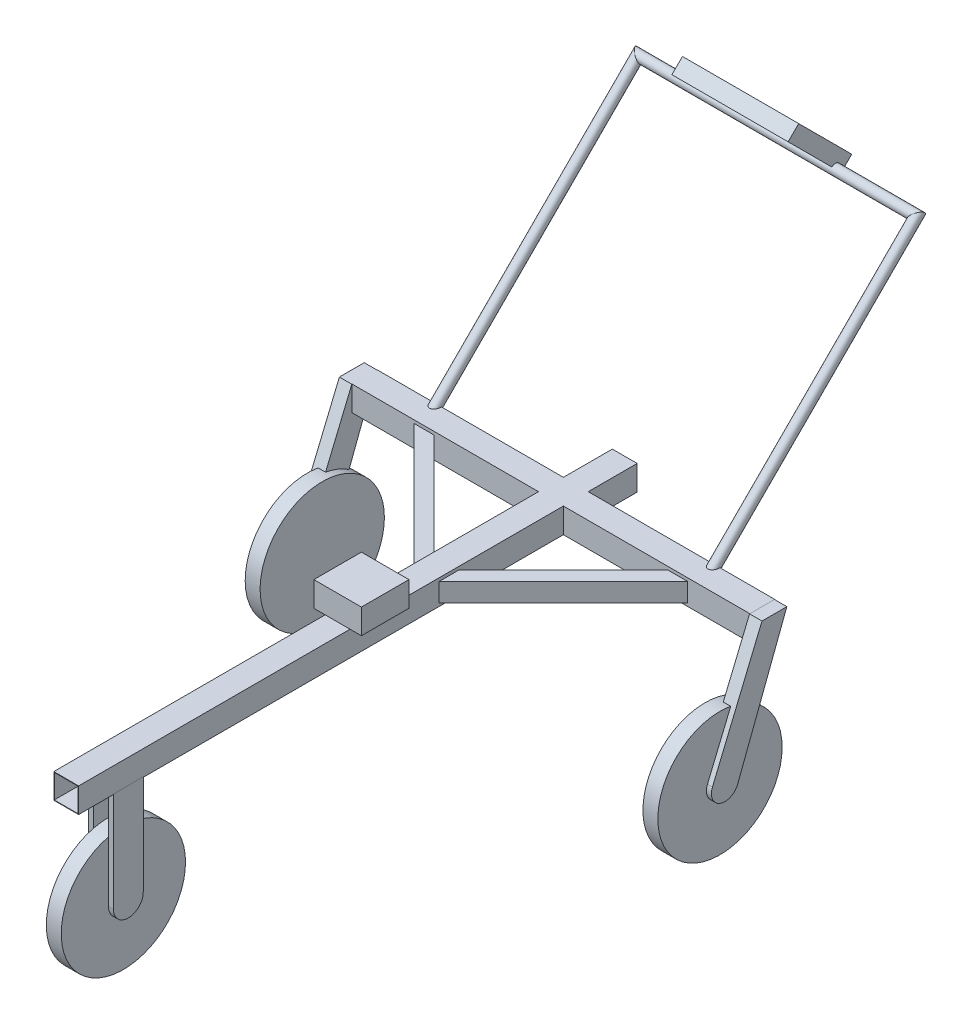
SolidWorks part; units mm, degrees
ref_plane "Front Plane" through (0, 0, 0) normal (0, 0, 1) x (1, 0, 0)
ref_plane "Top Plane" through (0, 0, 0) normal (0, 1, 0) x (1, 0, 0)
ref_plane "Right Plane" through (0, 0, 0) normal (1, 0, 0) x (0, 0, -1)
ref_plane "GROUND-WL" through (0, 0, 0) normal (0, 1, 0) x (1, 0, 0)
ref_plane "CL-BL" through (0, 0, 0) normal (1, 0, 0) x (0, 0, -1)
ref_plane "WHEEL-RAD-WL" through (0, 125, 0) normal (0, 1, 0) x (1, 0, 0)
ref_plane "FRAME-WL" through (0, 350, 0) normal (0, 1, 0) x (1, 0, 0)
ref_plane "REAR-WHEEL-STA" through (0, 0, 0) normal (0, 0, 1) x (1, 0, 0)
ref_plane "FRONT-WHEEL-STA" through (0, 0, 800) normal (0, 0, 1) x (1, 0, 0)
ref_plane "LEFT-WHEEL-BL" through (400, 0, 0) normal (1, 0, 0) x (0, 0, -1)
ref_plane "RIGHT-WHEEL-BL" through (-400, 0, 0) normal (1, 0, 0) x (0, 0, -1)
ref_plane "REAR-FRAME-BEAM-STA" through (0, 0, -100) normal (0, 0, 1) x (1, 0, 0)
ref_axis "REAR-WHEEL-AXIS" through (88.99, 125, 0) along (-1, 0, 0)
ref_axis "FRONT-WHEEL-AXIS" through (-88.99, 125, 800) along (1, 0, 0)
sketch "frame-sketch" plane through (0, 350, 0) normal (0, 1, 0) x (1, 0, 0)
  line L0 (-400, 100) -> (400, 100)
  line L1 (0, -900) -> (0, 140.9199)
  line L2 (280, 100) -> (0, -180)
  line L3 (-280, 100) -> (0, -180)
  line L4 (0, -55) -> (0, 55) construction
  line L6 (-55, 100) -> (55, 100) construction
  line L7 (400, -55) -> (400, 55) construction
  line L8 (-400, -55) -> (-400, 55) construction
  line L9 (-55, -800) -> (55, -800) construction
  dimension "D1" = 45
  dimension "D2" = 100
  dimension "D3" = 45
  dimension "D4" = 280
  dimension "D5" = 800
sketch "front-wheel-sketch" plane through (0, 0, 0) normal (1, 0, 0) x (0, 0, -1)
  circle A0 centre (-800, 125) radius 125
  dimension "D1" = 250
sketch "rear-left-wheel-sketch" plane through (400, 0, 0) normal (1, 0, 0) x (0, 0, -1)
  circle A0 centre (0, 125) radius 125
  dimension "D1" = 250
sketch "rear-right-wheel-sketch" plane through (-400, 0, 0) normal (1, 0, 0) x (0, 0, -1)
  circle A0 centre (0, 125) radius 125
  dimension "D1" = 250
ref_plane "HANDLE-PLANE" through (0, 125, 125) normal (0, 0.7071, 0.7071) x (1, 0, 0)
sketch "fwd-aft-beam-xs" plane through (0, 0, 0) normal (0, 0, 1) x (1, 0, 0)
  line L1 (-25, 325) -> (25, 325)
  line L2 (-25, 325) -> (-25, 375)
  line L3 (-25, 375) -> (25, 375)
  line L4 (25, 325) -> (25, 375)
  line L5 (-25, 325) -> (25, 375) construction
  line L6 (-25, 375) -> (25, 325) construction
  line L7 (-24, 326) -> (24, 326)
  line L8 (-24, 326) -> (-24, 374)
  line L9 (-24, 374) -> (24, 374)
  line L10 (24, 326) -> (24, 374)
  line L11 (-24, 326) -> (24, 374) construction
  line L12 (-24, 374) -> (24, 326) construction
  point P0 (0, 350)
  point P7 (0, 350)
  dimension "D1" = 50
  dimension "D2" = 50
  dimension "D3" = 1
sketch "fwd-aft-beam-profile" plane through (0, 350, -250) normal (0, -1, 0) x (1, 0, 0)
  line L1 (0, 1150) -> (0, 109.0801) construction
  line L2 (0, 1150) -> (0, 26.581)
  point P2 (0, 29.0267)
  point P4 (0, 26.581)
sketch "lat-beam-xs" plane through (0, 0, 0) normal (1, 0, 0) x (0, 0, -1)
  line L1 (75, 325) -> (125, 325)
  line L2 (75, 325) -> (75, 375)
  line L3 (75, 375) -> (125, 375)
  line L4 (125, 325) -> (125, 375)
  line L5 (75, 325) -> (125, 375) construction
  line L6 (75, 375) -> (125, 325) construction
  line L7 (76, 326) -> (124, 326)
  line L8 (76, 326) -> (76, 374)
  line L9 (76, 374) -> (124, 374)
  line L10 (124, 326) -> (124, 374)
  line L11 (76, 326) -> (124, 374) construction
  line L12 (76, 374) -> (124, 326) construction
  point P0 (100, 350)
  point P5 (100, 350)
  dimension "D1" = 50
  dimension "D2" = 50
  dimension "D3" = 1
sketch "lat-beam-profile" plane through (0, 350, 0) normal (0, 1, 0) x (1, 0, 0)
  line L0 (-400, 100) -> (400, 100) construction
  line L1 (-400, 100) -> (400, 100)
sweep "fwd-aft-beam" add profiles "fwd-aft-beam-xs" path "fwd-aft-beam-profile"
sweep "lat-beam" add profiles "lat-beam-xs" path "lat-beam-profile"
extrude "Boss-Extrude1" add sketch "front-wheel-sketch" along normal mid plane 30 separate body contours A0
extrude "Boss-Extrude2" add sketch "rear-right-wheel-sketch" along normal mid plane 30 separate body contours A0
extrude "Boss-Extrude3" add sketch "rear-left-wheel-sketch" along normal mid plane 30 separate body contours A0
sketch "Sketch1" plane through (0, 125, 125) normal (0, 0.7071, 0.7071) x (1, 0, 0)
  line L0 (-400, 318.1981) -> (400, 318.1981) construction
  line L1 (-400, 318.1981) -> (400, 318.1981) construction
  line L2 (280, 318.1981) -> (0, 120.2082) construction
  line L3 (-280, 318.1981) -> (0, 120.2082) construction
  line L4 (280, 318.1981) -> (0, 120.2082) construction
  line L5 (-280, 318.1981) -> (0, 120.2082) construction
  line L6 (-280, 318.1981) -> (-280, 926.61)
  line L7 (-280, 926.61) -> (280, 926.61)
  line L8 (280, 926.61) -> (280, 318.1981)
sweep "Sweep1" add path "Sketch1" circular profile diameter 20 parameters "D3"=20
sketch "Sketch14" plane through (0, 0, -100) normal (0, 0, 1) x (1, 0, 0)
  line L0 (280, 350) -> (0, 350) construction
  line L1 (-280, 350) -> (0, 350) construction
  line L2 (280, 350) -> (0, 350)
  line L3 (-280, 350) -> (0, 350)
  line L5 (-300.1301, 331.358) -> (-259.8699, 331.358)
  line L6 (-300.1301, 331.358) -> (-300.1301, 368.642)
  line L7 (-300.1301, 368.642) -> (-259.8699, 368.642)
  line L8 (-259.8699, 331.358) -> (-259.8699, 368.642)
  line L9 (-300.1301, 331.358) -> (-259.8699, 368.642) construction
  line L10 (-300.1301, 368.642) -> (-259.8699, 331.358) construction
  line L11 (259.2963, 331.358) -> (300.7037, 331.358)
  line L12 (259.2963, 331.358) -> (259.2963, 368.642)
  line L13 (259.2963, 368.642) -> (300.7037, 368.642)
  line L14 (300.7037, 331.358) -> (300.7037, 368.642)
  line L15 (259.2963, 331.358) -> (300.7037, 368.642) construction
  line L16 (259.2963, 368.642) -> (300.7037, 331.358) construction
sweep "Sweep2" add profiles "Sketch14" path "frame-sketch"
sketch "Sketch16" plane through (0, 0, 0) normal (1, 0, 0) x (0, 0, -1)
  line L0 (-800, 405.9305) -> (-800, -84.1787) construction
  line L1 (-800, 55) -> (-800, -55) construction
  line L2 (-830, 375) -> (-770, 375)
  line L3 (-770, 375) -> (-770, 125)
  line L5 (-830, 125) -> (-830, 375)
  line L6 (223.419, 375) -> (-900, 375)
  line L7 (223.419, 375) -> (-900, 375) construction
  line L8 (74.4636, 375) -> (124.4636, 375)
  line L9 (124.4636, 375) -> (25.5271, 115.276)
  line L11 (-25.2193, 135.4965) -> (74.4636, 375)
  arc A0 (-830, 125) -> (-770, 125) centre (-800, 125) ccw
  arc A1 (-25.2193, 135.4965) -> (25.5271, 115.276) centre (0, 125) ccw
  point P10 (-800, 375)
  point P18 (0, 0)
  point P20 (0, 0)
  point P21 (22.3994, 375)
  point P22 (119.4977, 375)
  point P23 (0, 0)
  point P24 (124.4636, 375)
  dimension "D2" = 50
  dimension "D1" = 60
extrude "Boss-Extrude4" add sketch "Sketch16" against normal up to surface (-15 mm away) from surface separate body contours L3 A0 L5 L2 up to face at (15, 125, 675) starting at face at (25, 350, 155)
extrude "Boss-Extrude5" add sketch "Sketch16<3>" against normal up to surface (-400 mm away) and the other way blind 10 from surface separate body contours L11 A1 L9 L8 region at (0, 236.0656, -44.4978) up to plane "LEFT-WHEEL-BL" starting at face at (415, 125, -125)
sketch "Sketch16<3>" plane through (0, 0, 0) normal (1, 0, 0) x (0, 0, -1) same geometry as "Sketch16"
ref_plane "Plane2" through (0, 655.2122, -655.2122) normal (0, -0.7071, 0.7071) x (1, 0, 0)
sketch "Sketch17" plane through (0, 655.2122, -655.2122) normal (0, -0.7071, 0.7071) x (1, 0, 0)
  line L0 (0, -55) -> (0, 55) construction
  line L1 (116.8854, 311.2104) -> (-116.8854, 311.2104)
  line L2 (116.8854, 311.2104) -> (116.8854, 160.2232)
  line L3 (116.8854, 160.2232) -> (-116.8854, 160.2232)
  line L4 (-116.8854, 311.2104) -> (-116.8854, 160.2232)
  line L5 (116.8854, 311.2104) -> (-116.8854, 160.2232) construction
  line L6 (116.8854, 160.2232) -> (-116.8854, 311.2104) construction
  point P0 (0, 235.7168)
  point P5 (0, 0)
extrude "Boss-Extrude6" add sketch "Sketch17" against normal blind 30
mirror "Mirror7" about plane through (0, 0, 0) normal (1, 0, 0) of "Boss-Extrude5", "Boss-Extrude4"
sketch "Sketch20" plane through (0, 375, 0) normal (0, 1, 0) x (1, 0, 0)
  line L0 (0, -55) -> (0, 55) construction
  line L1 (47.8177, -354.071) -> (-47.8177, -354.071)
  line L2 (47.8177, -354.071) -> (47.8177, -258.4356)
  line L3 (47.8177, -258.4356) -> (-47.8177, -258.4356)
  line L4 (-47.8177, -354.071) -> (-47.8177, -258.4356)
  line L5 (47.8177, -354.071) -> (-47.8177, -258.4356) construction
  line L6 (47.8177, -258.4356) -> (-47.8177, -354.071) construction
  point P0 (0, -306.2533)
  point P5 (0, 0)
extrude "Boss-Extrude7" add sketch "Sketch20" along normal blind 50
equation "\"wheel_rad\"= 125"
equation "\"clearance_wheel_frame\"= 100"
equation "\"D1@WHEEL-RAD-WL\" = \"wheel_rad\""
equation "\"D1@FRAME-WL\" = 2 * \"wheel_rad\" + \"clearance_wheel_frame\""
equation "\"rear_wheel_separation\"= 800"
equation "\"front_wheel_offset\"= 800"
equation "\"D1@FRONT-WHEEL-STA\" = \"front_wheel_offset\""
equation "\"D1@LEFT-WHEEL-BL\" = \"rear_wheel_separation\" / 2"
equation "\"D1@RIGHT-WHEEL-BL\" = \"rear_wheel_separation\" / 2"
equation "\"rear_frame_beam_offset\"= 100"
equation "\"D1@REAR-FRAME-BEAM-STA\"=\"rear_frame_beam_offset\""
equation "\"fwd_beam_overshoot\"= 100"
equation "\"D2@frame-sketch\" = \"fwd_beam_overshoot\""
equation "\"D3@frame-sketch\" = \"D1@frame-sketch\""
equation "\"D4@frame-sketch\" = .7 * \"D5@frame-sketch\" / 2"
equation "\"wheel_width\"= 30"
equation "\"D1@front-wheel-sketch\" = \"wheel_rad\" * 2"
equation "\"D1@rear-left-wheel-sketch\" = \"wheel_rad\" * 2"
equation "\"D1@rear-right-wheel-sketch\" = \"wheel_rad\" * 2"
equation "\"frame_xs_edge\"= 50"
equation "\"D1@fwd-aft-beam-xs\" = \"frame_xs_edge\""
equation "\"D2@fwd-aft-beam-xs\" = \"D1@fwd-aft-beam-xs\""
equation "\"D1@lat-beam-xs\" = \"frame_xs_edge\""
equation "\"D2@lat-beam-xs\" = \"D1@lat-beam-xs\""
equation "\"D2@Sketch16\"=\"frame_xs_edge\""
